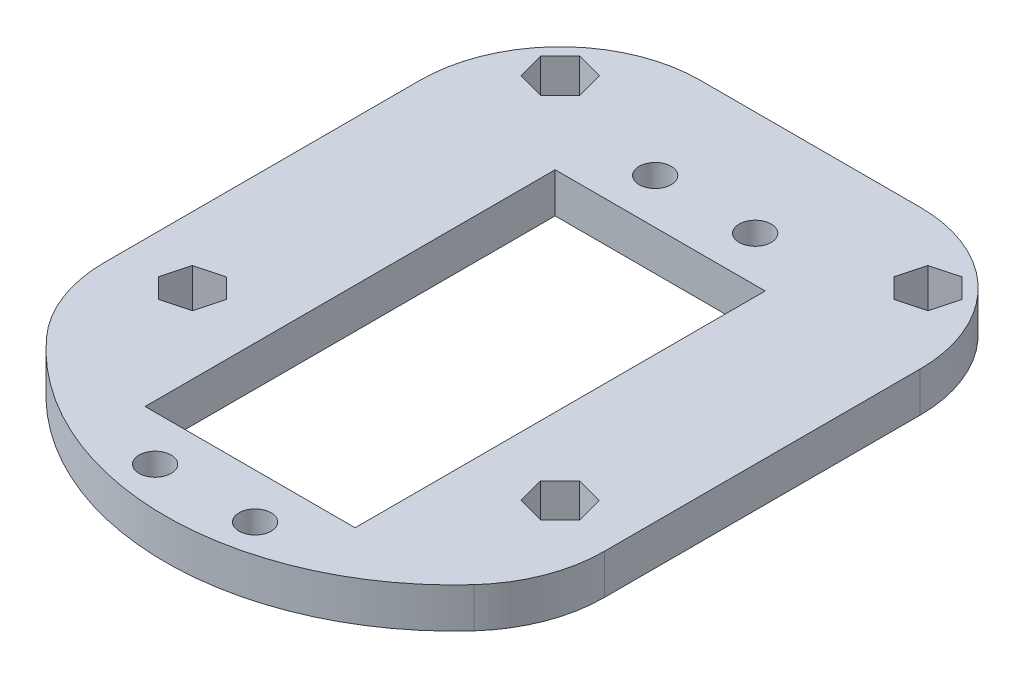
SolidWorks part; units mm, degrees
ref_plane "前视基准面" through (0, 0, 0) normal (0, 0, 1) x (1, 0, 0)
ref_plane "上视基准面" through (0, 0, 0) normal (0, 1, 0) x (1, 0, 0)
ref_plane "右视基准面" through (0, 0, 0) normal (1, 0, 0) x (0, 0, -1)
sketch "草图1" plane through (0, 0, 0) normal (0, 1, 0) x (1, 0, 0)
  line L0 (15.7082, 17.6676) -> (17.6679, 15.7081)
  line L1 (-18.385, 18.385) -> (18.385, 18.385) construction
  line L2 (-18.385, 18.385) -> (-18.385, -18.385) construction
  line L3 (-18.385, -18.385) -> (18.385, -18.385) construction
  line L4 (18.385, 18.385) -> (18.385, -18.385) construction
  line L5 (-18.385, 18.385) -> (18.385, -18.385) construction
  line L6 (-18.385, -18.385) -> (18.385, 18.385) construction
  line L7 (-17.6676, 15.7082) -> (-15.7081, 17.6679)
  line L8 (-15.7081, 17.6679) -> (-16.4255, 20.3447)
  line L9 (-16.4255, 20.3447) -> (-19.1024, 21.0618)
  line L10 (-19.1024, 21.0618) -> (-21.0619, 19.1021)
  line L11 (-21.0619, 19.1021) -> (-20.3445, 16.4253)
  line L12 (-20.3445, 16.4253) -> (-17.6676, 15.7082)
  line L13 (17.6679, 15.7081) -> (20.3447, 16.4255)
  line L14 (20.3447, 16.4255) -> (21.0618, 19.1024)
  line L15 (21.0618, 19.1024) -> (19.1021, 21.0619)
  line L16 (19.1021, 21.0619) -> (16.4253, 20.3445)
  line L17 (16.4253, 20.3445) -> (15.7082, 17.6676)
  line L18 (17.6676, -15.7082) -> (15.7081, -17.6679)
  line L19 (15.7081, -17.6679) -> (16.4255, -20.3447)
  line L20 (16.4255, -20.3447) -> (19.1024, -21.0618)
  line L21 (19.1024, -21.0618) -> (21.0619, -19.1021)
  line L22 (21.0619, -19.1021) -> (20.3445, -16.4253)
  line L23 (20.3445, -16.4253) -> (17.6676, -15.7082)
  line L24 (-15.7082, -17.6676) -> (-17.6679, -15.7081)
  line L25 (-17.6679, -15.7081) -> (-20.3447, -16.4255)
  line L26 (-20.3447, -16.4255) -> (-21.0618, -19.1024)
  line L27 (-21.0618, -19.1024) -> (-19.1021, -21.0619)
  line L28 (-19.1021, -21.0619) -> (-16.4253, -20.3445)
  line L29 (-16.4253, -20.3445) -> (-15.7082, -17.6676)
  line L31 (-25, 25) -> (25, 25)
  line L32 (-25, 25) -> (-25, -25)
  line L33 (-25, -25) -> (25, -25)
  line L34 (25, 25) -> (25, -25)
  line L35 (-25, 25) -> (25, -25) construction
  line L36 (-25, -25) -> (25, 25) construction
  circle A0 centre (-18.385, 18.385) radius 2.4 construction
  circle A1 centre (18.385, 18.385) radius 2.4 construction
  circle A2 centre (18.385, -18.385) radius 2.4 construction
  circle A3 centre (-18.385, -18.385) radius 2.4 construction
  point P0 (0, 0)
  point P6 (0, 0)
  point P40 (0, 0)
  dimension "D1" = 36.77
  dimension "D2" = 36.77
  dimension "D3" = 4.8
  dimension "D5" = 50
  dimension "D6" = 50
  dimension "D4" = 4
extrude "凸台-拉伸1" add sketch "草图1" along normal blind 4
sketch "草图2" plane through (0, 0, 0) normal (0, -1, 0) x (1, 0, 0)
  line L0 (0, -14.5) -> (0, 35.5) construction
  line L2 (-25, 25) -> (-10.5, 25)
  line L3 (-10.5, 31) -> (10.5, 31)
  line L4 (-10.5, 31) -> (-10.5, -10)
  line L5 (-10.5, -10) -> (10.5, -10)
  line L6 (10.5, 31) -> (10.5, -10)
  line L7 (-10.5, 31) -> (10.5, -10) construction
  line L8 (-10.5, -10) -> (10.5, 31) construction
  line L9 (-5, 35.5) -> (5, 35.5) construction
  line L10 (-5, 35.5) -> (-5, -14.5) construction
  line L11 (-5, -14.5) -> (5, -14.5) construction
  line L12 (5, 35.5) -> (5, -14.5) construction
  line L13 (-5, 35.5) -> (5, -14.5) construction
  line L14 (-5, -14.5) -> (5, 35.5) construction
  line L15 (-25, 25) -> (25, 25) construction
  line L16 (10.5, 25) -> (25, 25)
  arc A0 (-25, 25) -> (25, 25) centre (0, 10.6369) cw
  circle A1 centre (-5, 35.5) radius 1.6
  circle A2 centre (5, 35.5) radius 1.6
  circle A3 centre (-5, -14.5) radius 1.6
  circle A4 centre (5, -14.5) radius 1.6
  point P1 (0, 10.5)
  point P8 (0, 10.5)
  line M21 (25, 25) -> (-25, 25)
  dimension "D7" = 3.2
  dimension "D8" = 3.2
  dimension "D9" = 3.2
  dimension "D10" = 3.2
  dimension "D1" = 21
  dimension "D2" = 41
  dimension "D3" = 0
  dimension "D4" = 10
  dimension "D5" = 50
  dimension "D6" = 10
extrude "凸台-拉伸2" add sketch "草图2" against normal blind 4 contours A0 L4 L3 L6 M21 region at (0, 0, 31.7316)
extrude "切除-拉伸1" cut sketch "草图2<3>" against normal blind 4 contours L6 L4 L5 M21 | A3 | A4 region at (0, 0, 7.5)
sketch "草图2<3>" plane through (0, 0, 0) normal (0, -1, 0) x (1, 0, 0) same geometry as "草图2"
fillet "圆角1" radius 14 2 edges at (25, 2, -25) (-25, 2, -25)
fillet "圆角2" radius 14 2 edges at (25, 2, 25) (-25, 2, 25)
